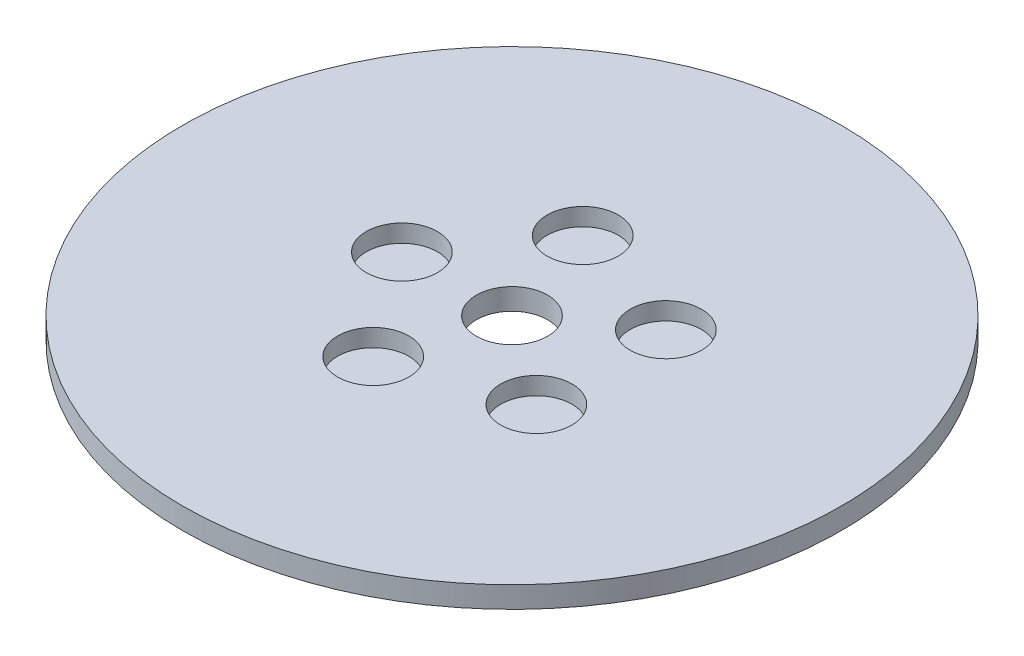
SolidWorks part; units mm, degrees
ref_plane "Front Plane" through (0, 0, 0) normal (0, 0, 1) x (1, 0, 0)
ref_plane "Top Plane" through (0, 0, 0) normal (0, 1, 0) x (1, 0, 0)
ref_plane "Right Plane" through (0, 0, 0) normal (1, 0, 0) x (0, 0, -1)
sketch "Sketch1" plane through (0, 0, 0) normal (0, 1, 0) x (1, 0, 0)
  circle A0 centre (0, 0) radius 92.5
  dimension "FLANGE_OD" = 185
extrude "Boss-Extrude1" add sketch "Sketch1" along normal blind 6
sketch "Sketch2" plane through (0, 0, 0) normal (0, 1, 0) x (1, 0, 0)
  circle A0 centre (0, 0) radius 10
  dimension "BORE_D" = 20
extrude "Cut-Extrude1" cut sketch "Sketch2" along normal through all
sketch "Sketch3" plane through (0, 6, 0) normal (0, 1, 0) x (1, 0, 0)
  circle A0 centre (0, 0) radius 30.9148 construction
  circle A1 centre (-30.9148, 0) radius 10
  dimension "BOLT_D" = 20
  dimension "BOLT_PCD" = 61.8296
extrude "Cut-Extrude2" cut sketch "Sketch3" against normal blind 4.942
pattern_circular "CirPattern1" count 5 over 360 about axis through (0, 0, 0) along (0, 1, 0) of "Cut-Extrude2"
